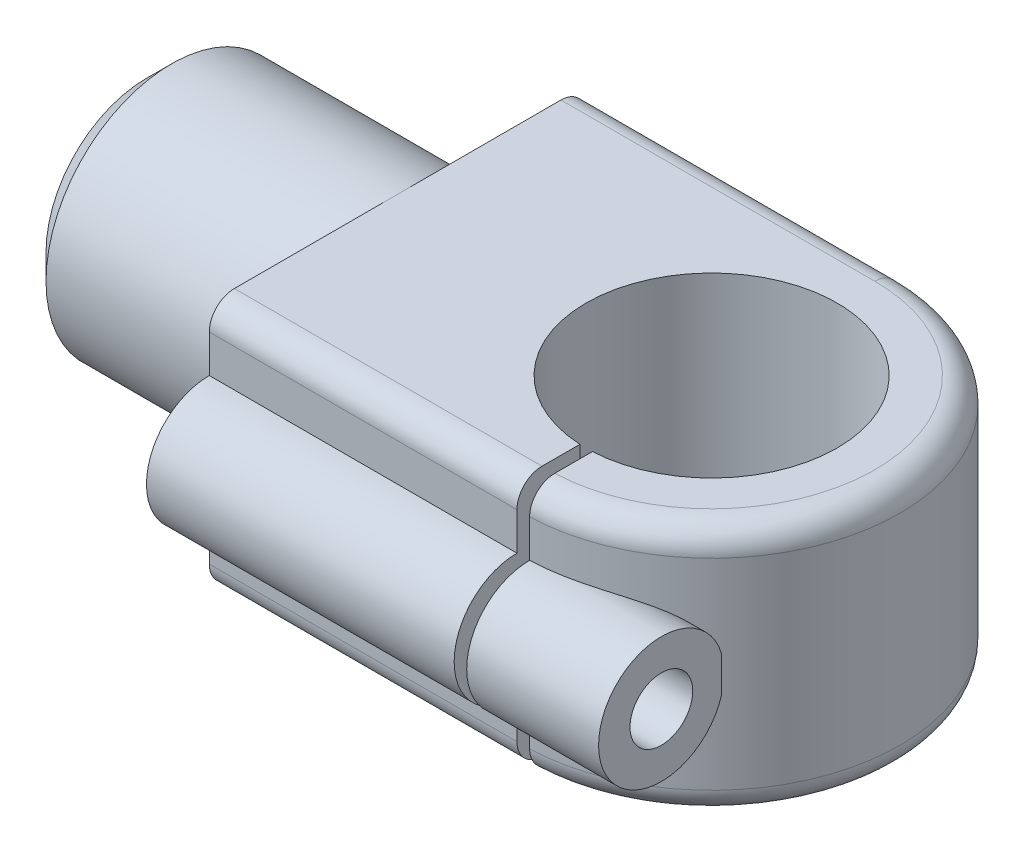
SolidWorks part; units mm, degrees
ref_plane "Front Plane" through (0, 0, 0) normal (0, 0, 1) x (1, 0, 0)
ref_plane "Top Plane" through (0, 0, 0) normal (0, 1, 0) x (1, 0, 0)
ref_plane "Right Plane" through (0, 0, 0) normal (1, 0, 0) x (0, 0, -1)
sketch "Sketch1" plane through (0, 0, 0) normal (0, 1, 0) x (1, 0, 0)
  line L0 (0, 15) -> (-30, 15)
  line L1 (-30, 15) -> (-30, -15)
  line L2 (-30, -15) -> (-0.5, -15)
  line L4 (0.5, -15) -> (0.5, -9.9875)
  line L5 (-0.5, -15) -> (-0.5, -9.9875)
  arc A0 (0.5, -9.9875) -> (-0.5, -9.9875) centre (0, 0) ccw
  arc A1 (0.5, -14.9917) -> (0, 15) centre (0, 0) ccw
  dimension "D1" = 20
  dimension "D2" = 30
  dimension "D3" = 30
extrude "Boss-Extrude1" add sketch "Sketch1" along normal blind 20 contours L4 A1 L0 L1 L2 L5 A0 region at (-12.0415, 0, -0.0669)
sketch "Sketch2" plane through (-30, 0, 0) normal (-1, 0, 0) x (0, 0, 1)
  line L0 (15, 20) -> (15, 0) construction
  circle A0 centre (15, 10) radius 5
  dimension "D1" = 10
extrude "Boss-Extrude2" add sketch "Sketch2" against normal blind 41
sketch "Sketch3" plane through (0, 20, 0) normal (0, 1, 0) x (1, 0, 0)
  line L0 (-0.5, -15) -> (-0.5, -9.9875) construction
  line L1 (0.5, -14.9917) -> (0.5, -9.9875) construction
  line L2 (-0.5, -15) -> (-0.5, -9.9875)
  line L3 (0.5, -14.9917) -> (0.5, -9.9875)
  line L4 (-0.5, -9.9875) -> (0.5, -9.9875)
  line L6 (-0.5, -15) -> (-0.5, -20)
  line L7 (-30, -20) -> (11, -20) construction
  line L8 (-0.5, -20) -> (0.5, -20)
  line L9 (0.5, -20) -> (0.5, -14.9917)
extrude "Cut-Extrude1" cut sketch "Sketch3" against normal blind 41
sketch "Sketch4" plane through (11, 0, 0) normal (1, 0, 0) x (0, 0, -1)
  circle A0 centre (-15, 10) radius 2.5
  dimension "D1" = 5
extrude "Cut-Extrude2" cut sketch "Sketch4" against normal through all
fillet "Fillet1" radius 2 6 edges at (-15, 0, -15) (-15, 20, -15) (-15.25, 20, 15) (-15.25, 0, 15) (14.9979, 0, -0.25) (14.9979, 20, -0.25)
sketch "Sketch5" plane through (-30, 0, 0) normal (-1, 0, 0) x (0, 0, 1)
  circle A0 centre (0, 10) radius 10
  dimension "D1" = 20
extrude "Boss-Extrude3" add sketch "Sketch5" along normal blind 15
sketch "Sketch6" plane through (-30, 0, 0) normal (-1, 0, 0) x (0, 0, 1)
  line L3 (0, 20) -> (-13, 20)
  line L4 (0, 0) -> (13, 0)
  line L5 (15, 2) -> (15, 5)
  line L6 (15, 15) -> (15, 18)
  line L7 (13, 20) -> (0, 20)
  line L8 (0, 0) -> (13, 0)
  line L9 (15, 2) -> (15, 5)
  line L10 (15, 15) -> (15, 18)
  line L11 (13, 20) -> (0, 20)
  line L12 (-15, 18) -> (-15, 2)
  line L13 (-13, 0) -> (0, 0)
  line L14 (0, 20) -> (-13, 20)
  line L15 (-15, 18) -> (-15, 2)
  line L16 (-13, 0) -> (0, 0)
  arc A3 (0, 20) -> (0, 0) centre (0, 10) ccw
  arc A4 (0, 0) -> (0, 20) centre (0, 10) ccw
  arc A5 (13, 0) -> (15, 2) centre (13, 2) ccw
  arc A6 (15, 5) -> (15, 15) centre (15, 10) ccw
  arc A7 (15, 18) -> (13, 20) centre (13, 18) ccw
  arc A8 (0, 0) -> (0, 20) centre (0, 10) ccw
  arc A9 (13, 0) -> (15, 2) centre (13, 2) ccw
  arc A10 (15, 5) -> (15, 15) centre (15, 10) ccw
  arc A11 (15, 18) -> (13, 20) centre (13, 18) ccw
  arc A12 (-13, 20) -> (-15, 18) centre (-13, 18) ccw
  arc A13 (-15, 2) -> (-13, 0) centre (-13, 2) ccw
  arc A14 (0, 20) -> (0, 0) centre (0, 10) ccw
  arc A15 (-13, 20) -> (-15, 18) centre (-13, 18) ccw
  arc A16 (-15, 2) -> (-13, 0) centre (-13, 2) ccw
  arc M15 (0, 20) -> (0, 0) centre (0, 10) cw
  line M16 (0, 0) -> (13, 0)
  arc M17 (13, 0) -> (15, 2) centre (13, 2) ccw
  line M18 (15, 2) -> (15, 5)
  arc M19 (15, 5) -> (15, 15) centre (15, 10) ccw
  line M20 (15, 15) -> (15, 18)
  arc M21 (15, 18) -> (13, 20) centre (13, 18) ccw
  line M22 (13, 20) -> (0, 20)
  dimension "D1" = 0
  dimension "D2" = 0
extrude "Cut-Extrude3" cut sketch "Sketch6" against normal blind 5 contours L15 A16 L16 A14 L14 A15 | M22 M15 M16 M17 M18 M19 M20 M21 region at (-30, 10, -11.0362) region at (-30, 10, 12.3604)
chamfer "Chamfer1" distance 2 angle 45 1 edges at (-45, 10, 10)
